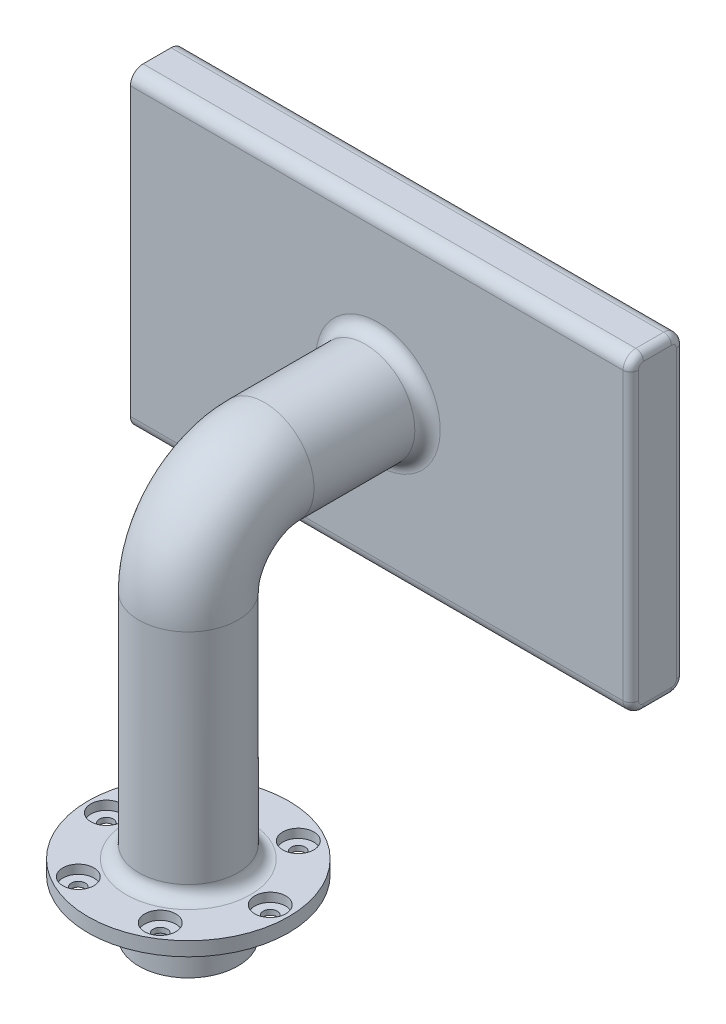
SolidWorks part; units mm, degrees
ref_plane "Front Plane" through (0, 0, 0) normal (0, 0, 1) x (1, 0, 0)
ref_plane "Top Plane" through (0, 0, 0) normal (0, 1, 0) x (1, 0, 0)
ref_plane "Right Plane" through (0, 0, 0) normal (1, 0, 0) x (0, 0, -1)
sketch "Sketch3" plane through (0, 0, 0) normal (1, 0, 0) x (0, 0, -1)
  line L0 (0, 0) -> (0, 52.5)
  line L1 (0, 0) -> (0, -52.5)
  line L2 (0, 0) -> (45.3348, 0) construction
  line L3 (21, -52.5) -> (21, -61.3564)
  line L5 (0, 52.5) -> (0, 61.3564)
  line L6 (0, 61.3564) -> (21, 61.3564)
  line L7 (21, 52.5) -> (21, 61.3564)
  line L8 (0, -52.5) -> (0, -61.3564)
  line L9 (0, -61.3564) -> (21, -61.3564)
  line L10 (21, 52.5) -> (19, 52.5)
  line L11 (19, 52.5) -> (19, 57.3564)
  line L12 (19, 57.3564) -> (4, 57.3564)
  line L13 (4, 57.3564) -> (4, -57.3564)
  line L14 (4, -57.3564) -> (19, -57.3564)
  line L15 (19, -57.3564) -> (19, -52.5)
  line L16 (19, -52.5) -> (21, -52.5)
  point P14 (19.5516, 52.5)
  dimension "D2" = 15
  dimension "D1" = 105
  dimension "D3" = 2
  dimension "D4" = 4
  dimension "D5" = 15
  dimension "D6" = 2
  dimension "D7" = 4
  dimension "D8" = 4
extrude "Boss-Extrude1" add sketch "Sketch3" along normal mid plane 195
fillet "Fillet4" radius 5 2 edges at (0, 61.3564, -21) (0, 61.3564, 0)
fillet "Fillet5" radius 5 2 edges at (0, 57.3564, -19) (0, 57.3564, -4)
fillet "Fillet6" radius 5 4 edges at (0, -61.3564, -21) (0, -61.3564, 0) (0, -57.3564, -19) (0, -57.3564, -4)
ref_plane "Plane1" through (0, 0, 0) normal (1, 0, 0) x (0, 0, -1)
sketch "Sketch7" plane through (0, 0, 0) normal (0, 0, 1) x (1, 0, 0)
  circle A0 centre (0, 0) radius 19.5
  dimension "D1" = 39
sketch "Sketch8" plane through (0, 0, 0) normal (1, 0, 0) x (0, 0, -1)
  line L0 (0, 0) -> (-44.7052, 0)
  line L1 (0, 19.5) -> (0, -19.5) construction
  line L2 (-74.7052, -30) -> (-74.7052, -75)
  arc A0 (-44.7052, 0) -> (-74.7052, -30) centre (-44.7052, -30) ccw
  point P6 (0, 0)
  point P8 (0, 0)
  point P9 (0, 0)
  point P10 (0, 0)
  dimension "D1" = 30
  dimension "D2" = 45
sweep "Sweep1" add profiles "Sketch7" path "Sketch8"
sketch "Sketch10" plane through (0, -75, 0) normal (0, -1, 0) x (1, 0, 0)
  circle A3 centre (0, 74.7052) radius 19.5
  dimension "D1" = 39
extrude "Boss-Extrude2" add sketch "Sketch10" along normal blind 73
sketch "Sketch11" plane through (0, 0, 0) normal (1, 0, 0) x (0, 0, -1)
  line L0 (-74.7052, -148) -> (-74.7052, -124.1973) construction
  line L1 (-94.2052, -148) -> (-55.2052, -148) construction
  line L2 (-94.2052, -30) -> (-94.2052, -148) construction
  line L3 (-94.2052, -121.142) -> (-114.2052, -121.142)
  line L4 (-94.2052, -121.142) -> (-94.2052, -126.642)
  line L5 (-94.2052, -126.642) -> (-114.2052, -126.642)
  line L6 (-114.2052, -121.142) -> (-114.2052, -126.642)
  dimension "D1" = 5.5
  dimension "D2" = 20
revolve "Revolve1" add sketch "Sketch11" angle 360 about L0
fillet "Fillet8" radius 5 1 edges at (19.5, 0, 0)
fillet "Fillet9" radius 5 1 edges at (0, -121.142, 55.2052)
hole_wizard "CBORE for M5 Hex Head Bolt1" positions "3DSketch1" profile "Sketch12" counterbore size "M5" standard "ISO" end condition through all
sketch3d "3DSketch1"
  point P0 (-31.8244, -121.142, 75.1392)
sketch "Sketch12" plane through (-31.8244, -121.142, 75.1392) normal (1, 0, 0) x (0, 0, 1)
  line L0 (0, 0) -> (0, 26.858)
  line L1 (0, 26.858) -> (2.75, 26.858)
  line L3 (2.75, 26.858) -> (2.75, 3.5)
  line L4 (2.75, 3.5) -> (6.119, 3.5)
  line L5 (6.119, 3.5) -> (6.119, 0)
  line L7 (6.119, 0) -> (0, 0)
  line L11 (0, -6.35) -> (0, 107.95) construction
  dimension "Thru Hole Dia." = 5.5
  dimension "Thru Hole Depth" = 26.858
  dimension "C'Bore Dia." = 12.238
  dimension "C'Bore Depth" = 3.5
pattern_circular "CirPattern1" count 6 over 360 about axis through (0, -121.142, 74.7052) along (0, -1, 0) of "CBORE for M5 Hex Head Bolt1"
sketch "Sketch13" plane through (0, 0, -4) normal (0, 0, -1) x (-1, 0, 0)
  line L0 (-89.2558, 0) -> (87.4971, 0) construction
  text T0 "SMART METHODS"
extrude "Cut-Extrude1" cut sketch "Sketch13" against normal blind 0.4
sketch "Sketch14" plane through (97.5, 0, 0) normal (1, 0, 0) x (0, 0, -1)
  line L0 (21, 52.5) -> (21, -52.5)
  line L1 (21, -56.3564) -> (21, -52.5) construction
  line L2 (21, 52.5) -> (21, 56.3564) construction
  line L3 (16, 61.3564) -> (5, 61.3564) construction
  line L4 (0, 56.3564) -> (0, -56.3564) construction
  line L5 (5, -61.3564) -> (16, -61.3564) construction
  line L6 (21, -56.3564) -> (21, -52.5)
  line L7 (21, 52.5) -> (21, 56.3564)
  line L8 (16, 61.3564) -> (5, 61.3564)
  line L9 (0, 56.3564) -> (0, -56.3564)
  line L10 (5, -61.3564) -> (16, -61.3564)
  arc A0 (21, 56.3564) -> (16, 61.3564) centre (16, 56.3564) ccw construction
  arc A1 (5, 61.3564) -> (0, 56.3564) centre (5, 56.3564) ccw construction
  arc A2 (0, -56.3564) -> (5, -61.3564) centre (5, -56.3564) ccw construction
  arc A3 (16, -61.3564) -> (21, -56.3564) centre (16, -56.3564) ccw construction
  arc A4 (21, 56.3564) -> (16, 61.3564) centre (16, 56.3564) ccw
  arc A5 (5, 61.3564) -> (0, 56.3564) centre (5, 56.3564) ccw
  arc A6 (0, -56.3564) -> (5, -61.3564) centre (5, -56.3564) ccw
  arc A7 (16, -61.3564) -> (21, -56.3564) centre (16, -56.3564) ccw
extrude "Boss-Extrude3" add sketch "Sketch14" along normal blind 2
fillet "Fillet10" radius 3 8 edges at (99.5, -59.8919, -19.5355) (99.5, -61.3564, -10.5) (99.5, -59.8919, -1.4645) (99.5, 0, 0) (99.5, 59.8919, -1.4645) (99.5, 61.3564, -10.5) (99.5, 59.8919, -19.5355) (99.5, 0, -21)
fillet "Fillet11" radius 2 7 edges at (97.5, -55.9423, -17.4865) (97.5, -57.3564, -11.501) (97.5, -55.8919, -5.4645) (97.5, 55.9423, -17.4865) (97.5, 57.3564, -11.501) (97.5, 55.8919, -5.4645) (97.5, 0, -4)
